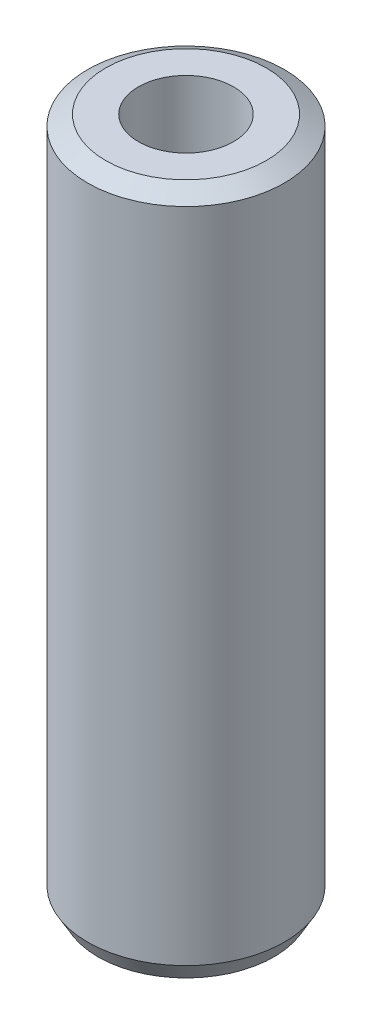
SolidWorks part; units mm, degrees
ref_plane "Front Plane" through (0, 0, 0) normal (0, 0, 1) x (1, 0, 0)
ref_plane "Top Plane" through (0, 0, 0) normal (0, 1, 0) x (1, 0, 0)
ref_plane "Right Plane" through (0, 0, 0) normal (1, 0, 0) x (0, 0, -1)
sketch "Sketch1" plane through (0, 0, 0) normal (0, 1, 0) x (1, 0, 0)
  circle A0 centre (0, 0) radius 35
  dimension "SHAFT_OD" = 70
extrude "Boss-Extrude1" add sketch "Sketch1" along normal blind 244.043
sketch "Sketch2" plane through (0, 0, 0) normal (0, 1, 0) x (1, 0, 0)
  circle A0 centre (0, 0) radius 16.9351
  dimension "BORE_D" = 33.8702
extrude "Cut-Extrude1" cut sketch "Sketch2" along normal through all
chamfer "Chamfer1" distance 3.7065 angle 60 2 edges at (0, 244.043, 35) (0, 0, 35) first distance on face at (0, 244.043, 35) first distance on face at (0, 0, 16.9351)
